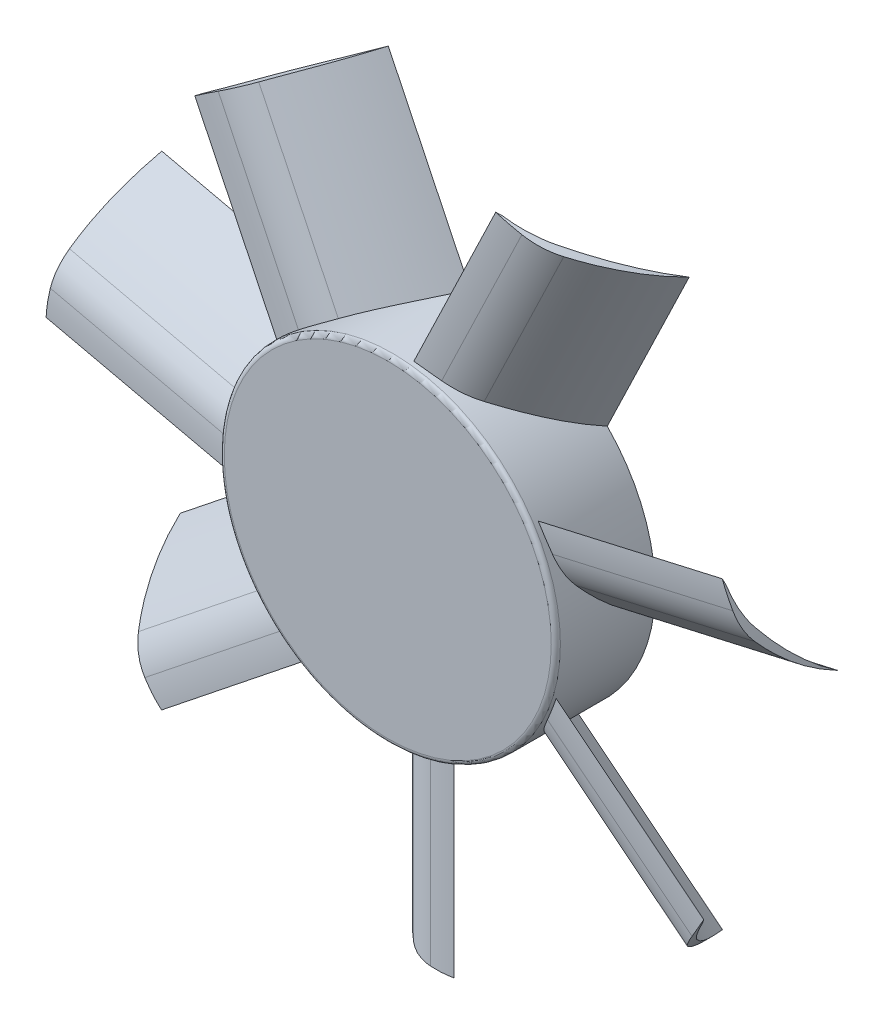
SolidWorks part; units mm, degrees
material "ПК/АБС"
ref_plane "Front" through (0, 0, 0) normal (0, 0, 1) x (1, 0, 0)
ref_plane "Top" through (0, 0, 0) normal (0, 1, 0) x (1, 0, 0)
ref_plane "Right" through (0, 0, 0) normal (1, 0, 0) x (0, 0, -1)
sketch "Эскиз1" plane through (0, 0, 0) normal (0, 0, 1) x (1, 0, 0)
  circle A0 centre (0, 0) radius 11
  dimension "D1" = 22
extrude "Бобышка-Вытянуть1" add sketch "Эскиз1" along normal blind 6.5
sketch "Эскиз2" plane through (0, 0, 0) normal (0, 0, -1) x (-1, 0, 0)
  circle A0 centre (0, 0) radius 9.75
  dimension "D1" = 19.5
extrude "Вырез-Вытянуть1" cut sketch "Эскиз2" against normal blind 5.5
sketch "Эскиз3" plane through (0, 0, 5.5) normal (0, 0, -1) x (-1, 0, 0)
  circle A0 centre (0, 0) radius 0.7
  dimension "D1" = 1.4
extrude "Бобышка-Вытянуть2" add sketch "Эскиз3" along normal blind 7.5
chamfer "Фаска1" distance 0.6 angle 45 1 edges at (-0.7, 0, -2)
sketch "Эскиз4" plane through (0, 0, 0) normal (0, 1, 0) x (1, 0, 0)
  line L0 (0, -6.5) -> (0, 0) construction
  line L1 (-11, -6.5) -> (11, -6.5) construction
  line L2 (0, 0) -> (11, -3.25) construction
  line L3 (11, -6.5) -> (11, 0) construction
  line L4 (11, -3.25) -> (-11, -3.25) construction
  line L5 (-11, 0) -> (-11, -6.5) construction
  line L7 (-3.75, -6.5) -> (3.75, -6.5) construction
  line L8 (-3.75, -6.5) -> (-3.75, 0) construction
  line L9 (-3.75, 0) -> (3.75, 0) construction
  line L10 (3.75, -6.5) -> (3.75, 0) construction
  line L11 (0, 0) -> (0, -6.5) construction
  line L12 (-3.75, -3.25) -> (3.75, -3.25) construction
  arc A2 (3.75, -5.9) -> (2.0764, -5.7876) centre (3.6109, 4.5482) cw
  arc A3 (0.0829, -4.887) -> (-3.75, 0) centre (9.9559, 6.8032) cw
  arc A4 (2.0764, -5.7876) -> (0.0829, -4.887) centre (2.6638, -1.831) cw
  arc A5 (3.75, -5.9) -> (3.4013, -5.7876) centre (6.34, 2.735) cw
  arc A6 (3.4013, -5.7876) -> (0.7393, -4.7108) centre (4.179, -0.0363) cw
  arc A7 (0.7393, -4.7108) -> (-3.75, 0) centre (11.8094, 10.3333) cw
  point P5 (0, -3.25)
  point P17 (3.4013, -5.7876)
  dimension "D3" = 0.6
  dimension "D4" = 4
  dimension "D1" = 6.5
  dimension "D2" = 7.5
extrude "Бобышка-Вытянуть3" add sketch "Эскиз4" against normal blind 23 from offset 10 offset against normal yes
pattern_circular "Круговой массив1" count 7 over 360 about axis through (0, 0, 6.5) along (0, 0, -1) of "Бобышка-Вытянуть3"
fillet "Скругление1" radius 0.3 1 edges at (11, 0, 6.5)
sketch "Эскиз5" plane through (0, 0, 6.5) normal (0, 0, 1) x (1, 0, 0)
  circle A0 centre (0, 0) radius 23
  dimension "D1" = 46
extrude "Вырез-Вытянуть2" cut sketch "Эскиз5" against normal blind 23 flip side to cut
